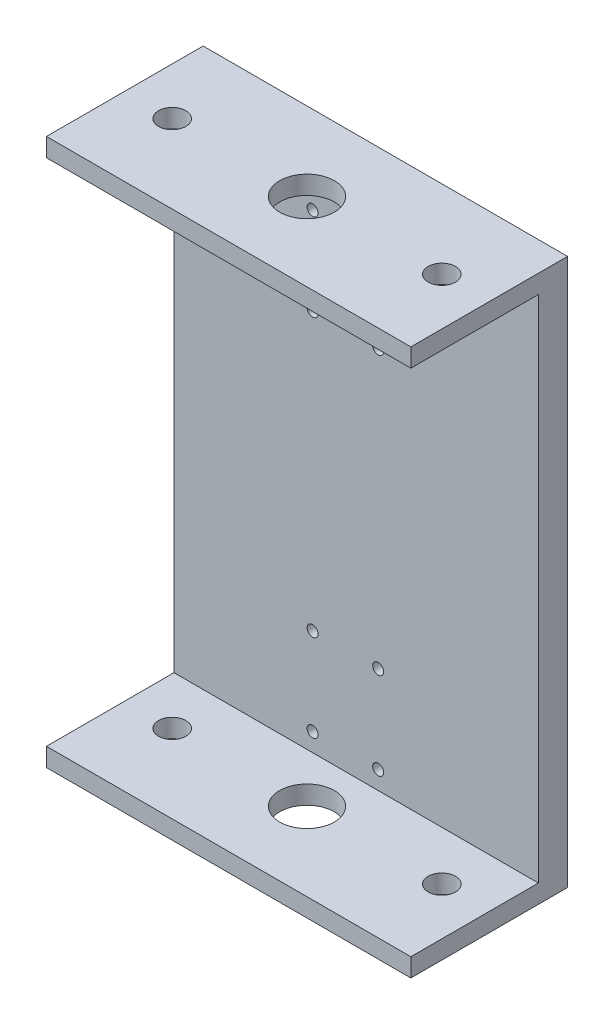
SolidWorks part; units mm, degrees
ref_plane "Front Plane" through (0, 0, 0) normal (0, 0, 1) x (1, 0, 0)
ref_plane "Top Plane" through (0, 0, 0) normal (0, 1, 0) x (1, 0, 0)
ref_plane "Right Plane" through (0, 0, 0) normal (1, 0, 0) x (0, 0, -1)
sketch "Sketch2" plane through (0, 0, 0) normal (0, 0, 1) x (1, 0, 0)
  line L6 (-53.365, 90) -> (46.635, 90)
  line L7 (-53.365, 90) -> (-53.365, -60)
  line L8 (-53.365, -60) -> (46.635, -60)
  line L9 (46.635, 90) -> (46.635, -60)
  line L10 (-53.365, 90) -> (46.635, -60) construction
  line L11 (-53.365, -60) -> (46.635, 90) construction
  circle A3 centre (-15.33, 74.0168) radius 1.5
  circle A7 centre (-15.33, -25.9832) radius 1.5
  circle A8 centre (-15.33, 50.0881) radius 1.5
  circle A9 centre (2.67, 50.0881) radius 1.5
  circle A10 centre (2.67, 74.0168) radius 1.5
  circle A11 centre (-15.33, -49.9119) radius 1.5
  circle A12 centre (2.67, -49.9119) radius 1.5
  circle A13 centre (2.67, -25.9832) radius 1.5
  point P5 (-3.365, 15)
  dimension "D3" = 100
extrude "Boss-Extrude1" add sketch "Sketch2" along normal blind 8
sketch "Sketch5" plane through (0, 0, 8) normal (0, 0, 1) x (1, 0, 0)
  line L6 (46.635, 90) -> (-53.365, 90)
  line L7 (-53.365, 90) -> (-53.365, 84.9336)
  line L8 (-53.365, 90) -> (-53.365, -60) construction
  line L9 (-53.365, 84.9336) -> (46.635, 84.9336)
  line L10 (46.635, -60) -> (46.635, 90) construction
  line L11 (46.635, 84.9336) -> (46.635, 90)
  line L12 (-13.365, -54.9336) -> (-53.365, -54.9336)
  line L15 (-13.365, -54.9336) -> (46.635, -54.9336)
  line L17 (46.635, -60) -> (-13.365, -60)
  line L18 (46.635, -54.9336) -> (46.635, -60)
  line L19 (-53.365, 90) -> (-53.365, -60) construction
  line L20 (-53.365, -54.9336) -> (-53.365, -60)
  line L21 (-53.365, -60) -> (-13.365, -60)
extrude "Boss-Extrude2" add sketch "Sketch5" along normal blind 35
sketch "Sketch7" plane through (0, 90, 0) normal (0, 1, 0) x (1, 0, 0)
  circle A0 centre (-3.365, -21.5) radius 7.5
  circle A1 centre (-40.365, -21.5) radius 3.75
  circle A2 centre (33.635, -21.5) radius 3.75
  point P12 (0, 0)
  dimension "D1" = 15
  dimension "D4" = 7.5
  dimension "D5" = 7.5
extrude "Cut-Extrude2" cut sketch "Sketch7" against normal blind 290
